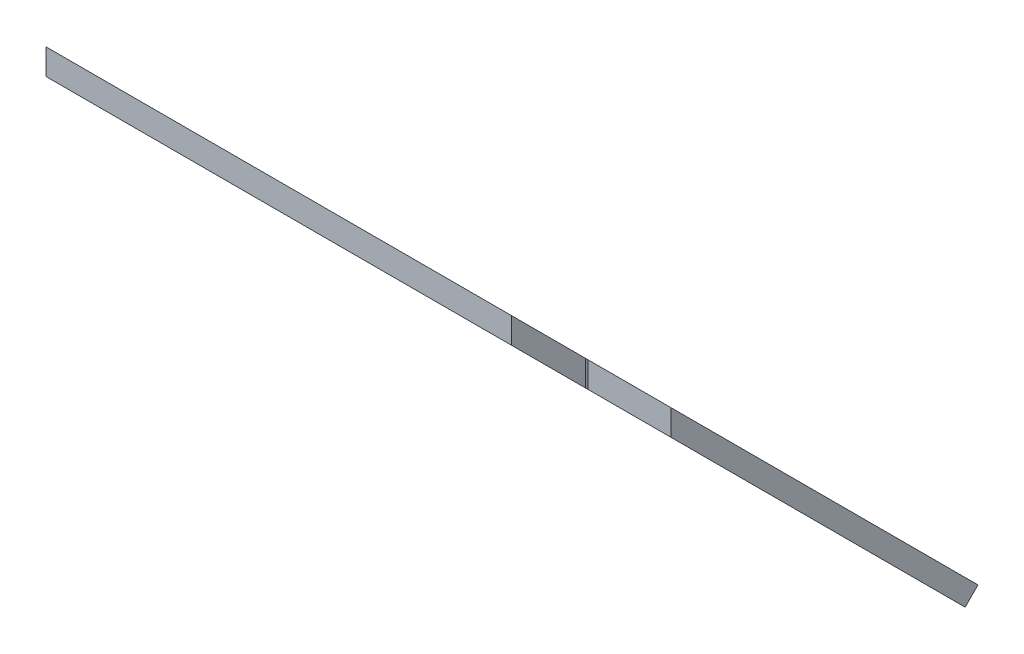
SolidWorks part; units mm, degrees
ref_plane "Front Plane" through (0, 0, 0) normal (0, 0, 1) x (1, 0, 0)
ref_plane "Top Plane" through (0, 0, 0) normal (0, 1, 0) x (1, 0, 0)
ref_plane "Right Plane" through (0, 0, 0) normal (1, 0, 0) x (0, 0, -1)
ref_axis "Axis1" through (-88.99, 0, 0) along (1, 0, 0)
ref_plane "Plane1" through (0, 0, 0) normal (0, -0.7071, 0.7071) x (1, 0, 0)
sketch "Sketch1" plane through (0, 0, 0) normal (0, -0.7071, 0.7071) x (1, 0, 0)
  line L0 (-88.99, 0) -> (88.99, 0) construction
  line L1 (-28.2668, 0) -> (-2.6636, 0)
  line L2 (-28.2668, 0) -> (-28.2668, -36.2534)
  line L3 (-28.2668, -36.2534) -> (-2.6636, -36.2534)
  line L4 (-2.6636, 0) -> (-2.6636, -36.2534)
  circle A0 centre (-15.3676, -27.2796) radius 5.1
  dimension "D3" = 10.2
  dimension "D1" = 25.6032
  dimension "D2" = 36.2534
  dimension "D4" = 27.2796
extrude "Boss-Extrude1" add sketch "Sketch1" along normal blind 1
sketch "Sketch2" plane through (0, 0, 0) normal (0, 1, 0) x (1, 0, 0)
  line L0 (-2.6636, 0) -> (-2.6636, 4.0665)
  line L1 (-2.6636, 25.635) -> (-2.6636, 0) construction
  line L2 (-2.6636, 4.0665) -> (-7.2356, 4.0665)
  line L3 (-7.2356, 4.0665) -> (-7.2356, 8.7655)
  line L4 (-7.2356, 8.7655) -> (-2.6636, 8.7655)
  line L5 (-2.6636, 8.7655) -> (3.6862, 8.7655)
  line L6 (3.6862, 8.7655) -> (3.6862, -11.023)
  line L7 (3.6862, -11.023) -> (-35.0538, -11.023)
  line L8 (-35.0538, -11.023) -> (-35.0538, 8.7655)
  line L9 (-35.0538, 8.7655) -> (-23.6948, 8.7655)
  line L10 (-23.6948, 8.7655) -> (-23.6948, 4.0665)
  line L11 (-23.6948, 4.0665) -> (-28.2668, 4.0665)
  line L12 (-28.2668, 0) -> (-28.2668, 25.635) construction
  line L13 (-28.2668, 4.0665) -> (-28.2668, 0)
  line L14 (-28.2668, 0) -> (-2.6636, 0)
  dimension "D1" = 4.699
  dimension "D2" = 4.699
  dimension "D3" = 4.572
  dimension "D4" = 4.572
  dimension "D5" = 4.0665
  dimension "D6" = 4.0665
extrude "Cut-Extrude1" cut sketch "Sketch2" against normal blind 50.8
